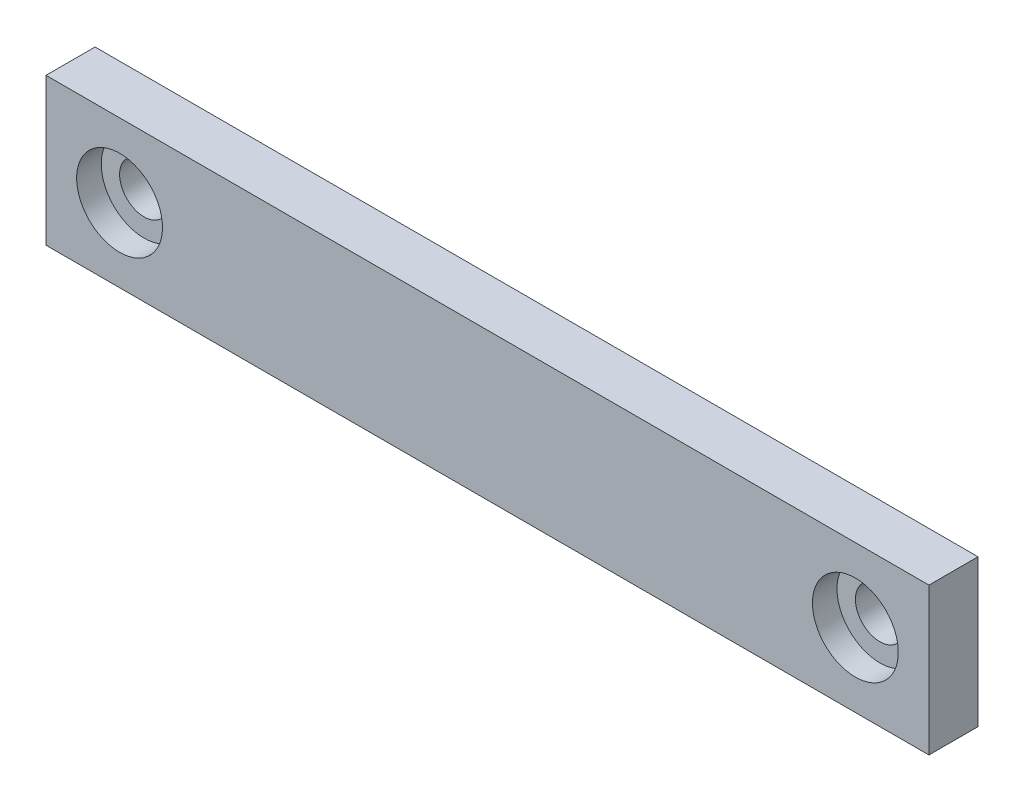
SolidWorks part; units mm, degrees
ref_plane "Přední rovina" through (0, 0, 0) normal (0, 0, 1) x (1, 0, 0)
ref_plane "Horní rovina" through (0, 0, 0) normal (0, 1, 0) x (1, 0, 0)
ref_plane "Pravá rovina" through (0, 0, 0) normal (1, 0, 0) x (0, 0, -1)
sketch "Skica1" plane through (0, 0, 0) normal (0, 0, 1) x (1, 0, 0)
  line L0 (0, 0) -> (0, 6) construction
  line L1 (0, 0) -> (36, 0) construction
  line L2 (-36, 6) -> (36, 6)
  line L3 (36, 6) -> (36, -6)
  line L4 (-36, -6) -> (36, -6)
  line L5 (-36, 6) -> (-36, -6)
  line L6 (0, 0) -> (-30, 0) construction
  circle A0 centre (-30, 0) radius 2
  circle A1 centre (30, 0) radius 2
  point P10 (0, -6)
  dimension "D4" = 4
  dimension "D1" = 36
  dimension "D2" = 72
  dimension "D3" = 12
  dimension "D5" = 30
extrude "Přidat vysunutím1" add sketch "Skica1" along normal blind 4
sketch "Skica2" plane through (0, 0, 4) normal (0, 0, 1) x (1, 0, 0)
  line L0 (-30, 0) -> (-30, 6) construction
  line L1 (36, 6) -> (-36, 6) construction
  line L2 (0, 0) -> (0, 6) construction
  circle A0 centre (-30, 0) radius 3.5
  circle A1 centre (30, 0) radius 3.5
  dimension "D1" = 7
extrude "Odebrat vysunutím1" cut sketch "Skica2" against normal blind 2
